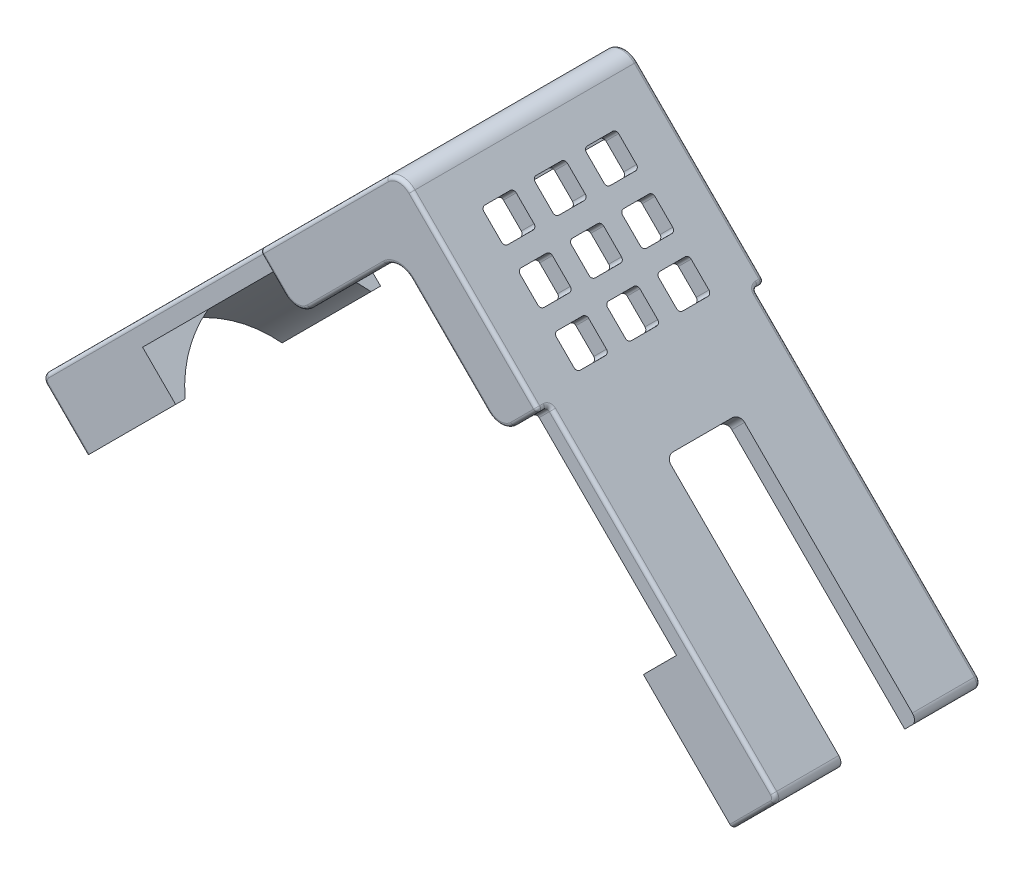
SolidWorks part; units mm, degrees
ref_plane "前视基准面" through (0, 0, 0) normal (0, 0, 1) x (1, 0, 0)
ref_plane "上视基准面" through (0, 0, 0) normal (0, 1, 0) x (1, 0, 0)
ref_plane "右视基准面" through (0, 0, 0) normal (1, 0, 0) x (0, 0, -1)
sketch "草图1" plane through (0, 0, 0) normal (0, 0, 1) x (1, 0, 0)
  line L0 (0, 53.346) -> (0, -57.0709) construction
  line L1 (0, 0) -> (-98.9949, -98.9949)
  line L2 (-98.9949, -98.9949) -> (-102.5305, -95.4594)
  line L3 (-102.5305, -95.4594) -> (0, 7.0711)
  line L4 (98.9949, -98.9949) -> (102.5305, -95.4594)
  line L5 (0, 0) -> (98.9949, -98.9949)
  line L6 (102.5305, -95.4594) -> (0, 7.0711)
  line L7 (-98.9949, -98.9949) -> (-84.8528, -113.1371)
  line L8 (-84.8528, -113.1371) -> (-60.1041, -88.3883)
  line L9 (-60.1041, -88.3883) -> (-74.2462, -74.2462)
  line L10 (98.9949, -98.9949) -> (84.8528, -113.1371)
  line L11 (84.8528, -113.1371) -> (60.1041, -88.3883)
  line L12 (60.1041, -88.3883) -> (74.2462, -74.2462)
  dimension "D1" = 45
  dimension "D2" = 5
  dimension "D3" = 140
  dimension "D4" = 20
  dimension "D5" = 35
extrude "凸台-拉伸1" add sketch "草图1" along normal blind 57 contours L0 L3 L2 L1 | L8 L9 L1 L7 | L6 L0 L5 L4 | L12 L11 L10 L5 region at (50.3865, -46.8303, 0) region at (-50.3865, -46.8303, 0) region at (-79.5495, -93.6916, 0) region at (79.5495, -93.6916, 0)
sketch "草图2" plane through (-98.9949, -98.9949, 0) normal (-0.7071, -0.7071, 0) x (0, 0, 1)
  line L0 (28.5, 5) -> (28.5, -55.5234) construction
  line L1 (57, 5) -> (0, 5) construction
  line L2 (-11.8515, -28.2) -> (75.3151, -28.2) construction
  line L3 (-1.5, -13) -> (58.5, -13)
  line L4 (-1.5, -13) -> (-1.5, -30.2015)
  line L5 (58.5, -13) -> (58.5, -30.2015)
  circle A0 centre (28.5, -28.2) radius 30
  point P11 (28.5, -13)
  line M3 (0, 5) -> (0, -20)
  line M4 (0, -20) -> (57, -20)
  line M5 (57, -20) -> (57, 5)
  dimension "D2" = 60
  dimension "D1" = 33.2
  dimension "D3" = 60
  dimension "D4" = 18
extrude "切除-拉伸1" cut sketch "草图2" against normal blind 57 contours A0 M5 M4 M3 | A0 L3 M5 M3 M4 | A0 L3 M3 | L3 A0 | A0 L3 M5 region at (-88.498, -109.4919, 0.839) region at (-73.0934, -124.8965, 28.5) region at (-94.0921, -103.8978, 28.5) region at (-87.2854, -110.7045, 28.5) region at (-88.498, -109.4919, 56.161)
mirror "镜向1" about plane through (0, 0, 0) normal (1, 0, 0) of "切除-拉伸1"
ref_plane "基准面1" through (0, 0, 28.5) normal (0, 0, -1) x (-1, 0, 0)
sketch "草图3" plane through (0, 0, 0) normal (0, 0, -1) x (-1, 0, 0)
  line L0 (0, 23.743) -> (0, -35.6833) construction
  line L1 (0, 7.0711) -> (-38.8909, -31.8198)
  line L2 (-102.5305, -95.4594) -> (0, 7.0711) construction
  line L3 (-38.8909, -31.8198) -> (-28.2843, -42.4264)
  line L4 (-28.2843, -42.4264) -> (0, -14.1421)
  line L5 (28.2843, -42.4264) -> (0, -14.1421)
  line L6 (38.8909, -31.8198) -> (28.2843, -42.4264)
  line L7 (0, 7.0711) -> (38.8909, -31.8198)
  dimension "D1" = 55
  dimension "D2" = 15
extrude "凸台-拉伸2" add sketch "草图3" along normal blind 3
mirror "镜向2" about plane through (0, 0, 28.5) normal (0, 0, -1) of "凸台-拉伸2"
sketch "草图4" plane through (0, 0, 0) normal (0.7071, -0.7071, 0) x (0, 0, -1)
  line L1 (-54.3643, -140) -> (-2.6357, -140) construction
  line L2 (-38.7352, -140) -> (-18.2648, -140)
  line L5 (-42.75, -8.7401) -> (-42.75, -48.6232) construction
  line L6 (-28.5, 0) -> (-28.5, -52.3884) construction
  line L7 (-38.7352, 0) -> (-18.2648, 0) construction
  line L8 (-28.5, -63.3921) -> (-28.5, 63.3921) construction
  line L9 (-14.25, -8.7401) -> (-14.25, -48.6232) construction
  line L10 (-54.9225, -28.2) -> (10.062, -28.2) construction
  line L11 (-53.9463, -13.95) -> (-2.907, -13.95) construction
  line L12 (-53.9463, -42.45) -> (-2.907, -42.45) construction
  line L14 (-46.25, -9.45) -> (-39.25, -9.45)
  line L15 (-47.25, -10.45) -> (-47.25, -17.45)
  line L16 (-46.25, -18.45) -> (-39.25, -18.45)
  line L17 (-38.25, -10.45) -> (-38.25, -17.45)
  line L18 (-42.75, -18.45) -> (-42.75, -9.45) construction
  line L19 (-47.25, -13.95) -> (-38.25, -13.95) construction
  line L51 (-24, -10.45) -> (-24, -17.45)
  line L52 (-32, -9.45) -> (-25, -9.45)
  line L53 (-33, -10.45) -> (-33, -17.45)
  line L54 (-32, -18.45) -> (-25, -18.45)
  line L55 (-9.75, -10.45) -> (-9.75, -17.45)
  line L56 (-17.75, -9.45) -> (-10.75, -9.45)
  line L57 (-18.75, -10.45) -> (-18.75, -17.45)
  line L58 (-17.75, -18.45) -> (-10.75, -18.45)
  line L59 (-24, -24.7) -> (-24, -31.7)
  line L60 (-32, -23.7) -> (-25, -23.7)
  line L61 (-33, -24.7) -> (-33, -31.7)
  line L62 (-32, -32.7) -> (-25, -32.7)
  line L63 (-9.75, -24.7) -> (-9.75, -31.7)
  line L64 (-17.75, -23.7) -> (-10.75, -23.7)
  line L65 (-18.75, -24.7) -> (-18.75, -31.7)
  line L66 (-17.75, -32.7) -> (-10.75, -32.7)
  line L67 (-24, -38.95) -> (-24, -45.95)
  line L68 (-32, -37.95) -> (-25, -37.95)
  line L69 (-33, -38.95) -> (-33, -45.95)
  line L70 (-32, -46.95) -> (-25, -46.95)
  line L71 (-9.75, -38.95) -> (-9.75, -45.95)
  line L72 (-17.75, -37.95) -> (-10.75, -37.95)
  line L73 (-18.75, -38.95) -> (-18.75, -45.95)
  line L74 (-17.75, -46.95) -> (-10.75, -46.95)
  line L75 (-38.25, -24.7) -> (-38.25, -31.7)
  line L76 (-46.25, -23.7) -> (-39.25, -23.7)
  line L77 (-47.25, -24.7) -> (-47.25, -31.7)
  line L78 (-46.25, -32.7) -> (-39.25, -32.7)
  line L79 (-38.25, -38.95) -> (-38.25, -45.95)
  line L80 (-46.25, -37.95) -> (-39.25, -37.95)
  line L81 (-47.25, -38.95) -> (-47.25, -45.95)
  line L82 (-46.25, -46.95) -> (-39.25, -46.95)
  line L83 (-38.7352, -140) -> (-38.7352, -70)
  line L84 (-38.7352, -70) -> (-18.2648, -70)
  line L85 (-18.2648, -70) -> (-18.2648, -140)
  arc A0 (-47.25, -10.45) -> (-46.25, -9.45) centre (-46.25, -10.45) cw
  arc A1 (-46.25, -18.45) -> (-47.25, -17.45) centre (-46.25, -17.45) cw
  arc A2 (-39.25, -18.45) -> (-38.25, -17.45) centre (-39.25, -17.45) ccw
  arc A3 (-38.25, -10.45) -> (-39.25, -9.45) centre (-39.25, -10.45) ccw
  arc A4 (-24, -10.45) -> (-25, -9.45) centre (-25, -10.45) ccw
  arc A5 (-33, -10.45) -> (-32, -9.45) centre (-32, -10.45) cw
  arc A6 (-32, -18.45) -> (-33, -17.45) centre (-32, -17.45) cw
  arc A7 (-25, -18.45) -> (-24, -17.45) centre (-25, -17.45) ccw
  arc A8 (-9.75, -10.45) -> (-10.75, -9.45) centre (-10.75, -10.45) ccw
  arc A9 (-18.75, -10.45) -> (-17.75, -9.45) centre (-17.75, -10.45) cw
  arc A10 (-17.75, -18.45) -> (-18.75, -17.45) centre (-17.75, -17.45) cw
  arc A11 (-10.75, -18.45) -> (-9.75, -17.45) centre (-10.75, -17.45) ccw
  arc A12 (-24, -24.7) -> (-25, -23.7) centre (-25, -24.7) ccw
  arc A13 (-33, -24.7) -> (-32, -23.7) centre (-32, -24.7) cw
  arc A14 (-32, -32.7) -> (-33, -31.7) centre (-32, -31.7) cw
  arc A15 (-25, -32.7) -> (-24, -31.7) centre (-25, -31.7) ccw
  arc A16 (-9.75, -24.7) -> (-10.75, -23.7) centre (-10.75, -24.7) ccw
  arc A17 (-18.75, -24.7) -> (-17.75, -23.7) centre (-17.75, -24.7) cw
  arc A18 (-17.75, -32.7) -> (-18.75, -31.7) centre (-17.75, -31.7) cw
  arc A19 (-10.75, -32.7) -> (-9.75, -31.7) centre (-10.75, -31.7) ccw
  arc A20 (-24, -38.95) -> (-25, -37.95) centre (-25, -38.95) ccw
  arc A21 (-33, -38.95) -> (-32, -37.95) centre (-32, -38.95) cw
  arc A22 (-32, -46.95) -> (-33, -45.95) centre (-32, -45.95) cw
  arc A23 (-25, -46.95) -> (-24, -45.95) centre (-25, -45.95) ccw
  arc A24 (-9.75, -38.95) -> (-10.75, -37.95) centre (-10.75, -38.95) ccw
  arc A25 (-18.75, -38.95) -> (-17.75, -37.95) centre (-17.75, -38.95) cw
  arc A26 (-17.75, -46.95) -> (-18.75, -45.95) centre (-17.75, -45.95) cw
  arc A27 (-10.75, -46.95) -> (-9.75, -45.95) centre (-10.75, -45.95) ccw
  arc A28 (-38.25, -24.7) -> (-39.25, -23.7) centre (-39.25, -24.7) ccw
  arc A29 (-47.25, -24.7) -> (-46.25, -23.7) centre (-46.25, -24.7) cw
  arc A30 (-46.25, -32.7) -> (-47.25, -31.7) centre (-46.25, -31.7) cw
  arc A31 (-39.25, -32.7) -> (-38.25, -31.7) centre (-39.25, -31.7) ccw
  arc A32 (-38.25, -38.95) -> (-39.25, -37.95) centre (-39.25, -38.95) ccw
  arc A33 (-47.25, -38.95) -> (-46.25, -37.95) centre (-46.25, -38.95) cw
  arc A34 (-46.25, -46.95) -> (-47.25, -45.95) centre (-46.25, -45.95) cw
  arc A35 (-39.25, -46.95) -> (-38.25, -45.95) centre (-39.25, -45.95) ccw
  point P25 (-42.75, -13.95)
  dimension "D5" = 1
  dimension "D1" = 14.25
  dimension "D2" = 14.25
  dimension "D3" = 14.25
  dimension "D4" = 14.25
  dimension "D6" = 9
  dimension "D9" = 9
  dimension "D10" = 70
  dimension "D7" = 3
  dimension "D8" = 3
extrude "切除-拉伸2" cut sketch "草图4" against normal blind 5
mirror "镜向3" about plane through (0, 0, 0) normal (1, 0, 0) of "切除-拉伸2"
fillet "圆角1" radius 5 1 edges at (0, 7.0711, 28.5)
fillet "圆角2" radius 5 6 edges at (-28.2843, -42.4264, 58.5) (0, -14.1421, 58.5) (28.2843, -42.4264, 58.5) (-28.2843, -42.4264, -1.5) (0, -14.1421, -1.5) (28.2843, -42.4264, -1.5)
fillet "圆角3" radius 2 4 edges at (-102.5305, -95.4594, 47.8676) (-102.5305, -95.4594, 9.1324) (102.5305, -95.4594, 47.8676) (102.5305, -95.4594, 9.1324)
fillet "圆角4" radius 1 18 edges at (35.3553, -35.3553, 60) (28.2843, -40.3553, 60) (14.1421, -28.2843, 60) (0, -16.2132, 60) (-14.1421, -28.2843, 60) (-28.2843, -40.3553, 60) (35.3553, -35.3553, -3) (28.2843, -40.3553, -3) (14.1421, -28.2843, -3) (0, -16.2132, -3) (-14.1421, -28.2843, -3) (-28.2843, -40.3553, -3) (37.1231, -33.5876, 57) (-35.3553, -35.3553, 60) (-37.1231, -33.5876, 57) (37.1231, -33.5876, 0) (-37.1231, -33.5876, 0) (-35.3553, -35.3553, -3)
fillet "圆角5" radius 1 30 edges at (-95.4594, -102.5305, 57) (-101.7021, -95.4594, 57) (-70.3571, -63.2861, 57) (-39.098, -32.0269, 57.2929) (-38.8909, -31.8198, 58.5) (-38.6838, -31.6127, 59.7071) (-20.8597, -13.7886, 60) (0, 5, 60) (95.4594, -102.5305, 57) (101.7021, -95.4594, 57) (70.3571, -63.2861, 57) (39.098, -32.0269, 57.2929) (38.8909, -31.8198, 58.5) (38.6838, -31.6127, 59.7071) (-95.4594, -102.5305, 0) (-101.7021, -95.4594, 0) (-70.3571, -63.2861, 0) (-39.098, -32.0269, -0.2929) (-38.8909, -31.8198, -1.5) (-38.6838, -31.6127, -2.7071) (-20.8597, -13.7886, -3) (0, 5, -3) (95.4594, -102.5305, 0) (101.7021, -95.4594, 0) (70.3571, -63.2861, 0) (39.098, -32.0269, -0.2929) (38.8909, -31.8198, -1.5) (38.6838, -31.6127, -2.7071) (20.8597, -13.7886, 60) (20.8597, -13.7886, -3)
fillet "圆角6" radius 2 4 edges at (51.2652, -47.7297, 18.2648) (51.2652, -47.7297, 38.7352) (-51.2652, -47.7297, 18.2648) (-51.2652, -47.7297, 38.7352)
